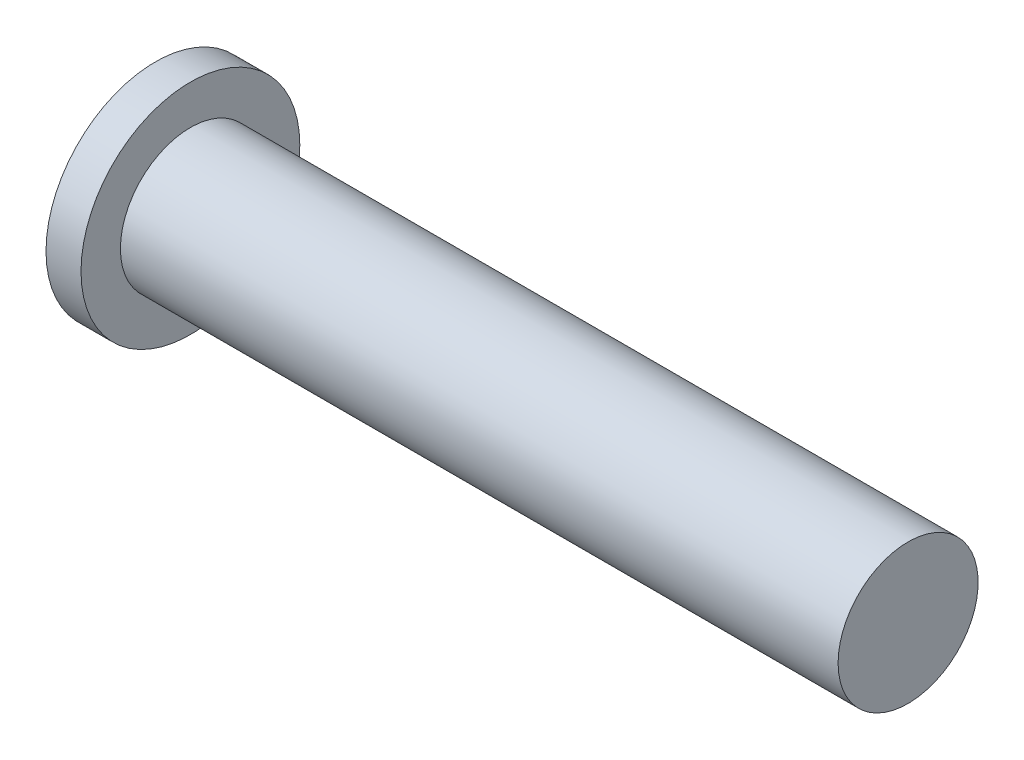
SolidWorks part; units mm, degrees
ref_plane "正面" through (0, 0, 0) normal (0, 0, 1) x (1, 0, 0)
ref_plane "平面" through (0, 0, 0) normal (0, 1, 0) x (1, 0, 0)
ref_plane "右側面" through (0, 0, 0) normal (1, 0, 0) x (0, 0, -1)
sketch "ｽｹｯﾁ1" plane through (0, 0, 0) normal (0, 1, 0) x (1, 0, 0)
  line L0 (0, 0) -> (146.5281, 0) construction
  line L1 (0, 0) -> (0, 6.25)
  line L2 (0, 6.25) -> (2, 6.25)
  line L3 (2, 6.25) -> (2, 4)
  line L4 (2, 4) -> (43, 4)
  line L5 (43, 4) -> (43, 0)
  line L6 (43, 0) -> (0, 0)
  dimension "D1" = 6.25
  dimension "D2" = 43
  dimension "D3" = 2
  dimension "D4" = 4
revolve "回転1" add sketch "ｽｹｯﾁ1" angle 360 about L0
